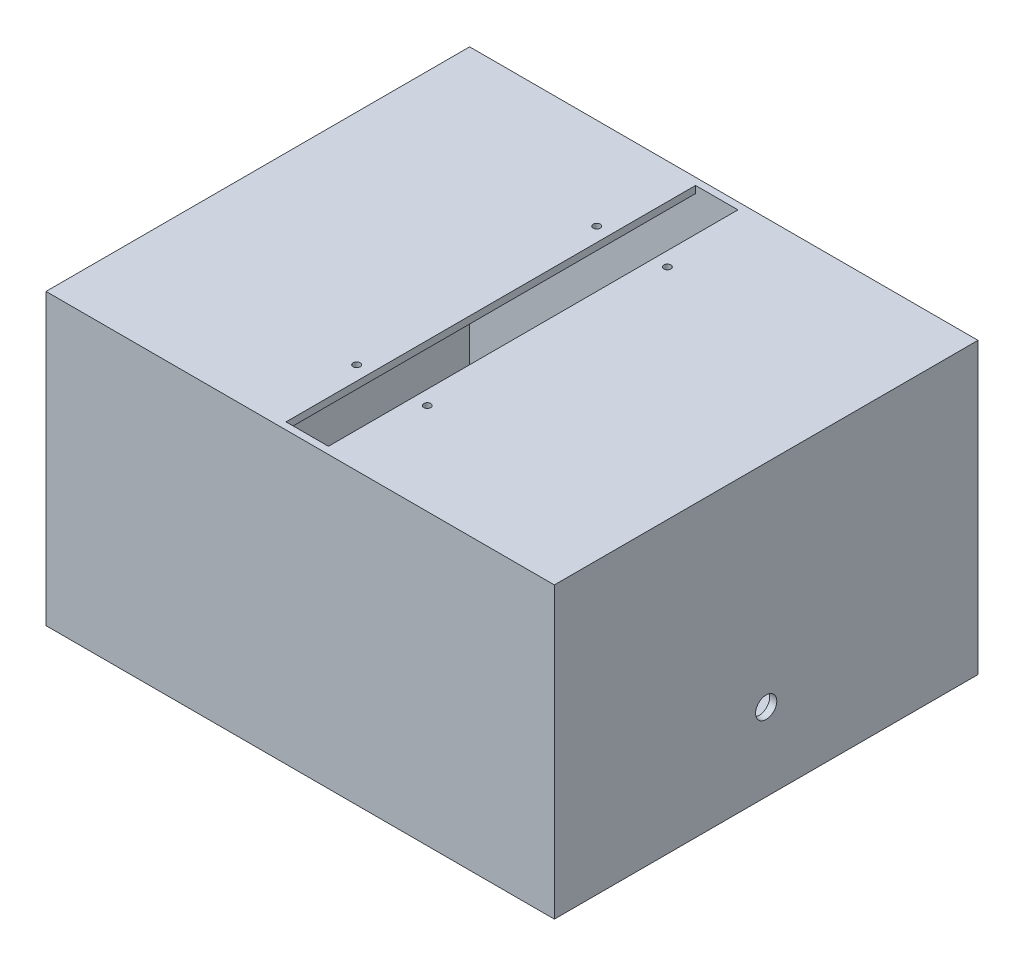
SolidWorks part; units mm, degrees
ref_plane "Front Plane" through (0, 0, 0) normal (0, 0, 1) x (1, 0, 0)
ref_plane "Top Plane" through (0, 0, 0) normal (0, 1, 0) x (1, 0, 0)
ref_plane "Right Plane" through (0, 0, 0) normal (1, 0, 0) x (0, 0, -1)
sketch "Sketch1" plane through (0, 0, 0) normal (0, 1, 0) x (1, 0, 0)
  line L0 (250, 0) -> (0, 0) construction
  line L1 (0, 0) -> (-250, 0) construction
  line L2 (-180, -150) -> (180, -150)
  line L3 (-180, -150) -> (-180, 150)
  line L4 (180, -150) -> (180, 150)
  line L5 (-180, 150) -> (180, 150)
  line L6 (-180, -150) -> (180, 150) construction
  line L7 (180, -150) -> (-180, 150) construction
  dimension "D1" = 300
  dimension "D2" = 360
extrude "Boss-Extrude1" add sketch "Sketch1" against normal blind 200
sketch "Sketch2" plane through (0, -200, 0) normal (0, -1, 0) x (1, 0, 0)
  line L0 (-180, 150) -> (180, 150) construction
  line L1 (-175, -145) -> (175, -145)
  line L2 (-175, -145) -> (-175, 145)
  line L3 (-175, 145) -> (175, 145)
  line L4 (175, -145) -> (175, 145)
  line L5 (-175, -145) -> (175, 145) construction
  line L6 (-175, 145) -> (175, -145) construction
  line L7 (180, 150) -> (180, -150) construction
  point P0 (0, 0)
  dimension "D1" = 5
  dimension "D2" = 5
extrude "Cut-Extrude1" cut sketch "Sketch2" against normal blind 195
sketch "Sketch3" plane through (0, 0, 0) normal (0, 1, 0) x (1, 0, 0)
  line L0 (-180, 0) -> (180, 0) construction
  line L1 (-180, 150) -> (-180, -150) construction
  line L2 (180, -150) -> (180, 150) construction
  line L3 (0, 150) -> (0, -120.2082) construction
  line L4 (-15, -145) -> (15, -145)
  line L5 (-15, -145) -> (-15, 145)
  line L6 (-15, 145) -> (15, 145)
  line L7 (15, -145) -> (15, 145)
  line L8 (-15, -145) -> (15, 145) construction
  line L9 (-15, 145) -> (15, -145) construction
  line L10 (180, 150) -> (-180, 150) construction
  point P6 (0, 0)
  dimension "D1" = 30
  dimension "D2" = 5
extrude "Cut-Extrude2" cut sketch "Sketch3" against normal through all
sketch "Sketch4" plane through (-180, 0, 0) normal (-1, 0, 0) x (0, 0, 1)
  line L0 (0, 0) -> (0, -200) construction
  line L1 (-150, -200) -> (150, -200) construction
  circle A0 centre (0, -150) radius 7.5
  point P7 (0, -100)
  point P8 (0, -100)
  point P10 (0, -150)
  dimension "D1" = 50
  dimension "D2" = 15
extrude "Cut-Extrude3" cut sketch "Sketch4" against normal through all
sketch "Sketch5" plane through (0, 0, 0) normal (0, 1, 0) x (1, 0, 0)
  line L0 (0, 150) -> (0, -150) construction
  line L1 (180, 150) -> (-180, 150) construction
  line L2 (-180, -150) -> (180, -150) construction
  line L3 (25, 150) -> (25, -150) construction
  line L4 (-25, 150) -> (-25, -150) construction
  line L5 (-180, 0) -> (180, 0) construction
  line L6 (-180, 150) -> (-180, -150) construction
  line L7 (180, -150) -> (180, 150) construction
  circle A0 centre (-25, 85) radius 2.5
  circle A1 centre (25, 85) radius 2.5
  circle A2 centre (25, -85) radius 2.5
  circle A3 centre (-25, -85) radius 2.5
  dimension "D4" = 5
  dimension "D1" = 25
  dimension "D2" = 25
  dimension "D3" = 85
extrude "Cut-Extrude4" cut sketch "Sketch5" against normal up to surface (5 mm away) up to face at (-95, -5, 0)
sketch "Sketch6" plane through (0, -200, 0) normal (0, -1, 0) x (1, 0, 0)
  line L1 (-180, 150) -> (180, 150)
  line L2 (-180, 150) -> (-180, -150)
  line L3 (-180, -150) -> (180, -150)
  line L4 (180, 150) -> (180, -150)
extrude "Boss-Extrude2" add sketch "Sketch6" along normal blind 5
sketch "Sketch7" plane through (0, 0, -150) normal (0, 0, -1) x (-1, 0, 0)
  line L0 (0, 0) -> (0, -205) construction
  line L1 (180, -205) -> (-180, -205) construction
  line L2 (-180, -200) -> (180, -200) construction
  line L3 (-180, -205) -> (-180, 0) construction
  line L4 (180, -205) -> (180, 0) construction
  line L6 (-100, -200) -> (100, -200)
  line L7 (-100, -200) -> (-100, -177)
  line L8 (-100, -177) -> (100, -177)
  line L9 (100, -200) -> (100, -177)
  line L10 (-100, -200) -> (100, -177) construction
  line L11 (-100, -177) -> (100, -200) construction
  point P11 (0, -188.5)
  dimension "D1" = 5
  dimension "D2" = 200
  dimension "D3" = 23
extrude "Cut-Extrude5" cut sketch "Sketch7" against normal up to surface (5 mm away) up to face at (0, -52.5, -145)
